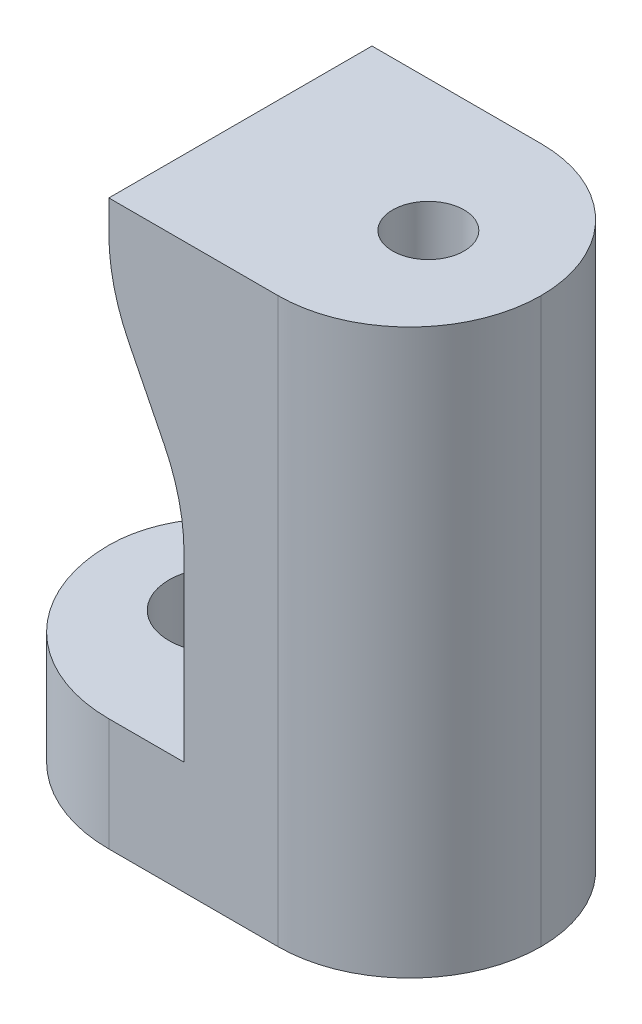
SolidWorks part; units mm, degrees
ref_plane "Plan de face" through (0, 0, 0) normal (0, 0, 1) x (1, 0, 0)
ref_plane "Plan de dessus" through (0, 0, 0) normal (0, 1, 0) x (1, 0, 0)
ref_plane "Plan de droite" through (0, 0, 0) normal (1, 0, 0) x (0, 0, -1)
sketch "Esquisse1" plane through (0, 0, 0) normal (0, 0, 1) x (1, 0, 0)
  line L0 (-2, 13) -> (0, 9)
  line L1 (0, 0) -> (-6, 0)
  line L2 (6, 15) -> (-2, 15)
  line L3 (0, 3) -> (-6, 3)
  line L4 (-6, 0) -> (-6, 3)
  line L5 (0, 0) -> (6, 0)
  line L6 (0, 3) -> (0, 9)
  line L8 (6, 0) -> (6, 15)
  line L12 (-2, 15) -> (-2, 13)
  dimension "D1" = 6
  dimension "D2" = 8
  dimension "D3" = 15
  dimension "D4" = 2
  dimension "D5" = 6
  dimension "D6" = 6
  dimension "D7" = 3
  dimension "D8" = 2
extrude "Boss.-Extru.1" add sketch "Esquisse1" along normal blind 7
sketch "Esquisse2" plane through (0, 3, 0) normal (0, 1, 0) x (1, 0, 0)
  line L1 (0, 0) -> (-6, 0) construction
  line L2 (-6, -7) -> (-6, 0) construction
  circle A0 centre (-3, -3) radius 1.4
  dimension "D1" = 2.8
  dimension "D2" = 3
  dimension "D3" = 3
extrude "Enlèv. mat.-Extru.1" cut sketch "Esquisse2" against normal through all
sketch "Esquisse3" plane through (0, 15, 0) normal (0, 1, 0) x (1, 0, 0)
  line L0 (6, 0) -> (-2, 0) construction
  line L1 (6, -7) -> (6, 0) construction
  circle A0 centre (3, -3.5) radius 0.95
  dimension "D1" = 1.9
  dimension "D2" = 3
  dimension "D3" = 3.5
extrude "Enlèv. mat.-Extru.2" cut sketch "Esquisse3" against normal blind 10
fillet "Congé1" radius 3 1 edges at (-6, 1.5, 0)
fillet "Congé2" radius 4 1 edges at (-6, 1.5, 7)
fillet "Congé3" radius 3.5 2 edges at (6, 7.5, 7) (6, 7.5, 0)
fillet "Congé4" radius 5 2 edges at (-2, 13, 3.5) (0, 9, 3.5)
